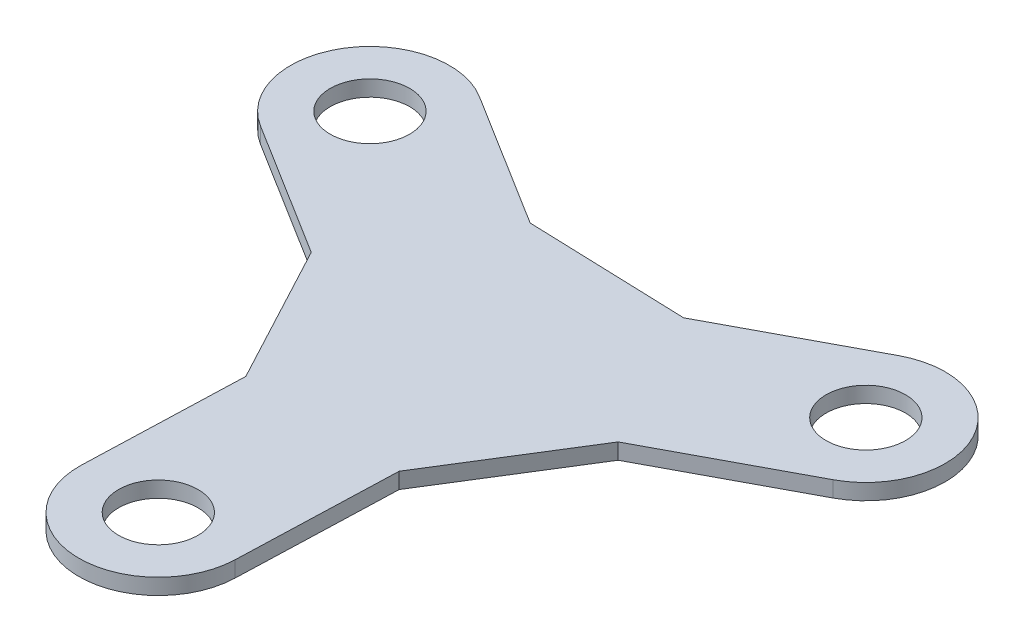
SolidWorks part; units mm, degrees
ref_plane "Front Plane" through (0, 0, 0) normal (0, 0, 1) x (1, 0, 0)
ref_plane "Top Plane" through (0, 0, 0) normal (0, 1, 0) x (1, 0, 0)
ref_plane "Right Plane" through (0, 0, 0) normal (1, 0, 0) x (0, 0, -1)
sketch "Sketch1" plane through (0, 0, 0) normal (0, 1, 0) x (1, 0, 0)
  line L1 (10.5808, 16.9719) -> (-9.4077, 17.6492)
  line L2 (-9.4077, 17.6492) -> (-19.9885, 0.6773)
  line L3 (-19.9885, 0.6773) -> (-10.5808, -16.9719)
  line L4 (-10.5808, -16.9719) -> (9.4077, -17.6492)
  line L5 (9.4077, -17.6492) -> (19.9885, -0.6773)
  line L6 (19.9885, -0.6773) -> (10.5808, 16.9719)
  circle A0 centre (0, 0) radius 17.3205 construction
  dimension "D1" = 20
base flange "Base-Flange1" sketch "Sketch1" thickness 2 reverse thickness direction no parameters "D1"=10
sketch "Sketch9" plane through (0, -2, 0) normal (0, -1, 0) x (1, 0, 0)
  line L0 (-10.5808, 16.9719) -> (-11.2581, 36.9605)
  line L1 (-11.2581, 36.9605) -> (8.7304, 37.6378) construction
  line L2 (8.7304, 37.6378) -> (9.4077, 17.6492)
  line L3 (9.4077, 17.6492) -> (-10.5808, 16.9719)
  line L4 (19.9885, 0.6773) -> (37.6378, -8.7304)
  line L5 (28.23, -26.3796) -> (10.5808, -16.9719)
  line L6 (10.5808, -16.9719) -> (19.9885, 0.6773)
  line L7 (-9.4077, -17.6492) -> (-26.3796, -28.23)
  line L8 (-36.9605, -11.2581) -> (-19.9885, -0.6773)
  line L9 (-19.9885, -0.6773) -> (-9.4077, -17.6492)
  arc A0 (8.7304, 37.6378) -> (-11.2581, 36.9605) centre (-1.2639, 37.2991) ccw
  circle A1 centre (-1.2639, 37.2991) radius 5
  arc A2 (28.23, -26.3796) -> (37.6378, -8.7304) centre (32.9339, -17.555) ccw
  circle A3 centre (32.9339, -17.555) radius 5
  arc A4 (-36.9605, -11.2581) -> (-26.3796, -28.23) centre (-31.67, -19.7441) ccw
  circle A5 centre (-31.67, -19.7441) radius 5
  point P23 (0, 0)
  dimension "D1" = 20
  dimension "D2" = 10
  dimension "D3" = 3
base flange "Tab1" sketch "Sketch9" thickness 2 reverse thickness direction no parameters "D1"=10
sketch "Bend-Lines1" [suppressed] plane through (0, 0, 0) normal (0, 1, 0) x (1, 0, 0)
sketch "Bounding-Box1" [suppressed] plane through (0, 0, 0) normal (0, 1, 0) x (1, 0, 0)
sheet metal parameters "Sheet-Metal1" thickness 2 parameters "D1"=10
flat pattern "Flat-Pattern1" [suppressed]
sketch "Bend-Lines2" plane through (0, 0, 0) normal (0, 1, 0) x (1, 0, 0)
sketch3d "Bounding-Box2" [suppressed]
  line L0 (-24.6924, 9.5019, 0) -> (-5.877, -25.7965, 0) construction
  line L1 (5.877, 25.7965, 0) -> (24.6924, -9.5019, 0) construction
  line L2 (-24.6924, 9.5019, 0) -> (5.877, 25.7965, 0) construction
  line L3 (-5.877, -25.7965, 0) -> (24.6924, -9.5019, 0) construction
sheet metal parameters "Sheet-Metal2" thickness 2 parameters "D1"=10
flat pattern "Flat-Pattern2"
sketch "Bend-Lines3" plane through (0, 0, 0) normal (0, 1, 0) x (1, 0, 0)
sketch3d "Bounding-Box3" [suppressed]
  line L0 (-45.1984, 23.8648, 0) -> (-5.3846, -50.8275, 0) construction
  line L1 (21.8517, 59.605, 0) -> (61.6654, -15.0874, 0) construction
  line L2 (-45.1984, 23.8648, 0) -> (21.8517, 59.605, 0) construction
  line L3 (-5.3846, -50.8275, 0) -> (61.6654, -15.0874, 0) construction
